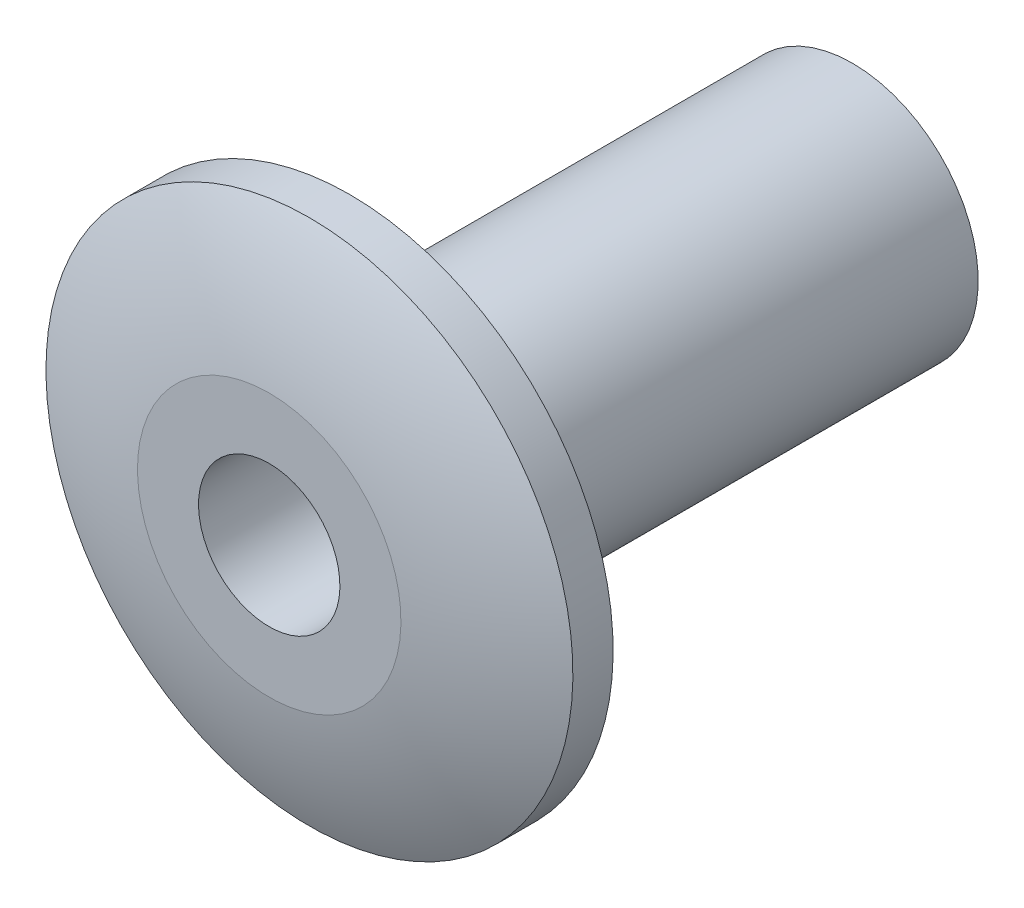
SolidWorks part; units mm, degrees
material "3003-H14"
ref_plane "Front" through (0, 0, 0) normal (0, 0, 1) x (1, 0, 0)
ref_plane "Top" through (0, 0, 0) normal (0, 1, 0) x (1, 0, 0)
ref_plane "Right" through (0, 0, 0) normal (1, 0, 0) x (0, 0, -1)
sketch "Sketch1" plane through (0, 0, 0) normal (1, 0, 0) x (0, 0, -1)
  line L0 (-10.541, 0) -> (-1.016, 0) construction
  line L1 (-1.016, 0) -> (0, 0) construction
  line L2 (0, 0) -> (6.35, 0) construction
  line L3 (6.35, 0) -> (7.874, 0) construction
  line L8 (0, 3.3274) -> (0, -3.3274) construction
  line L9 (6.35, 1.5875) -> (6.35, -1.5875) construction
  dimension "Length" = 6.35
  dimension "Head Height" = 1.016
  dimension "D5" = 1.524
  dimension "D9" = 9.525
  dimension "Diameter" = 3.175
  dimension "Head Diameter" = 6.6548
sketch "Sketch2" plane through (0, 0, 0) normal (1, 0, 0) x (0, 0, -1)
  line L0 (-10.541, 0.7937) -> (-10.541, 0) construction
  line L1 (-10.541, 0.7937) -> (0, 0.7937) construction
  line L2 (0, 3.3274) -> (0, -3.3274) construction
  line L3 (0, 0) -> (0, 3.3274) construction
  line L4 (-1.016, 0) -> (-1.016, -1.8472) construction
  line L5 (6.35, 1.5875) -> (0, 1.5875)
  line L6 (6.35, 1.5875) -> (6.35, 0) construction
  line L7 (7.874, 0) -> (7.874, 1.5875) construction
  line L8 (6.35, 1.5875) -> (6.35, 0)
  line L9 (7.874, 1.5875) -> (6.35, 1.5875) construction
  line L10 (-1.016, 0.893) -> (-1.016, 1.6637)
  line L11 (6.35, 0) -> (7.874, 0) construction
  line L12 (6.35, 0) -> (0.635, 0)
  line L13 (-1.016, 0.7937) -> (-1.016, 0) construction
  line L14 (6.35, 1.5875) -> (6.35, 0) construction
  line L15 (6.35, 1.5875) -> (6.35, 0) construction
  line L16 (6.35, 0) -> (6.35, 1.5875) construction
  line L17 (6.35, 1.5875) -> (6.35, 0) construction
  line L18 (6.35, 0) -> (6.35, 1.5875) construction
  line L19 (0, 1.5875) -> (0, 3.3274)
  line L20 (-1.016, 0.893) -> (0, 0.893)
  line L21 (-10.541, 0.893) -> (0, 0.893) construction
  line L22 (0, 3.3274) -> (-0.508, 3.3274)
  line L23 (0, 0.893) -> (0.635, 0.893)
  line L24 (0.635, 0.893) -> (0.635, 0)
  arc A0 (7.874, 0) -> (6.35, 1.27) centre (6.5828, 0) ccw construction
  arc A2 (-0.508, 3.3274) -> (-1.016, 1.6637) centre (4.8114, 0.7937) ccw
  dimension "D3" = 0.508
  dimension "D1" = 0.7937
  dimension "D2" = 0.635
  dimension "D5" = 1.27
  dimension "D6" = 1.6637
  dimension "D4" = 0.0992
revolve "Revolve1" add sketch "Sketch2" angle 360 about L12
sketch "Sketch7" plane through (0, 0, 0) normal (1, 0, 0) x (0, 0, -1)
  line L0 (-9.788, 0.7937) -> (0.635, 0.7937)
  line L1 (0.635, 0.893) -> (0.635, 0) construction
  line L2 (0.635, 0.7937) -> (0.635, 0)
  line L3 (0.635, 0) -> (-10.541, 0)
  line L5 (-10.417, 0.266) -> (-9.788, 0.7937)
  arc A0 (-10.541, 0) -> (-10.417, 0.266) centre (-10.1937, 0) cw
  dimension "D1" = 0.3473
  dimension "D2" = 40
revolve "Revolve2" [suppressed] add sketch "Sketch7" angle 360 about L0
sketch "Sketch8" plane through (0, 0, 0) normal (1, 0, 0) x (0, 0, -1)
  line L1 (6.35, 1.27) -> (6.35, 0)
  line L2 (6.35, 0) -> (7.874, 0) construction
  line L3 (7.874, 0) -> (6.5828, 0) construction
  line L4 (7.5512, 0) -> (6.35, 0)
  line L5 (6.35, 1.27) -> (6.6992, 1.27) construction
  arc A0 (7.874, 0) -> (6.35, 1.27) centre (6.5828, 0) ccw construction
  arc A1 (6.6993, 1.2859) -> (6.35, 1.27) centre (6.5828, 0) ccw
  arc A2 (6.6993, 1.2859) -> (7.5512, 0) centre (6.1548, 0) cw
  circle A3 centre (6.5828, 0) radius 1.2912 construction
  point P7 (7.5512, 0)
  point P8 (7.2284, 0)
  point P9 (6.9056, 0)
  point P12 (6.4664, 1.27)
  point P13 (6.5828, 1.27)
revolve "Revolve3" [suppressed] add sketch "Sketch8" angle 360 about L3
sketch "Sketch3" [suppressed] plane through (0, 0, 0) normal (0, 1, 0) x (1, 0, 0)
  line L0 (-0.997, -8.4087) -> (-0.2209, -10.541)
  line L1 (-0.2209, -10.541) -> (0.2209, -10.541)
  line L3 (0, -10.541) -> (0, -11.049) construction
  line L4 (0.266, -10.417) -> (-0.266, -10.417) construction
  line L5 (-0.997, -8.4087) -> (-0.997, -11.049)
  line L6 (-0.997, -11.049) -> (0.9969, -11.049)
  line L7 (0.9969, -11.049) -> (0.9969, -8.4087)
  line L8 (-0.7937, 0.635) -> (-0.7937, -9.788) construction
  line L9 (0, -10.541) -> (0, -1.016) construction
  line L10 (0.2209, -10.541) -> (0.9969, -8.4087)
  line L11 (-0.7937, -9.788) -> (-0.266, -10.417) construction
  arc A0 (-0.266, -10.417) -> (0.266, -10.417) centre (0, -10.1937) ccw construction
  point P11 (-0.266, -10.417)
  point P25 (0, -10.541)
  dimension "D1" = 40
  dimension "D2" = 0.2032
  dimension "D3" = 0.508
extrude "Cut-Extrude1" [suppressed] cut sketch "Sketch3" against normal through all both and the other way through all
pattern_circular "CirPattern1" [suppressed] count 2 every 90 about axis through (0, 0, 10.541) along (0, 0, -1) of bodies 111
sketch "Sketch9" [suppressed] plane through (0, 0, 0) normal (0, 1, 0) x (1, 0, 0)
  line L0 (0, -10.541) -> (0, 19.9517) construction
  line L1 (0, 6.35) -> (0, 7.874) construction
  line L2 (3.3274, 0) -> (-3.3274, 0) construction
  line L3 (2.0356, 0) -> (2.1341, 0)
  line L4 (2.0356, 0) -> (2.0356, 0.0254)
  line L5 (2.0356, 0.0254) -> (2.1341, 0.0254)
  line L6 (2.1341, 0) -> (2.1341, 0.0254)
  line L8 (2.3081, 0) -> (2.4066, 0)
  line L9 (2.3081, 0) -> (2.3081, 0.0254)
  line L10 (2.3081, 0.0254) -> (2.4066, 0.0254)
  line L11 (2.4066, 0) -> (2.4066, 0.0254)
  line L12 (2.551, 0) -> (2.6495, 0)
  line L13 (2.551, 0) -> (2.551, 0.0254)
  line L14 (2.551, 0.0254) -> (2.6495, 0.0254)
  line L15 (2.6495, 0) -> (2.6495, 0.0254)
  line L16 (2.9023, 0) -> (3.0008, 0)
  line L17 (2.9023, 0) -> (2.9023, 0.0254)
  line L18 (2.9023, 0.0254) -> (3.0008, 0.0254)
  line L19 (3.0008, 0) -> (3.0008, 0.0254)
  line L20 (1.9076, 0) -> (1.8091, 0)
  line L21 (1.9076, 0) -> (1.9076, 0.0254)
  line L22 (1.9076, 0.0254) -> (1.8091, 0.0254)
  line L23 (1.8091, 0) -> (1.8091, 0.0254)
  point P24 (2.9515, 0.0254)
  point P25 (2.6003, 0.0254)
  point P26 (2.3573, 0.0254)
  point P27 (2.0848, 0.0254)
  point P32 (1.8583, 0.0254)
  dimension "D1" = 0.0985
  dimension "D2" = 0.0254
  dimension "D3" = 5.903
  dimension "D4" = 5.2005
  dimension "D5" = 4.7146
  dimension "D6" = 4.1697
  dimension "D7" = 3.7167
revolve "Revolve4" [suppressed] add sketch "Sketch9" angle 360 about L0
equation "\"D5@Sketch1\" = \"Head Height@Sketch1\" * 1.5"
equation "\"D9@Sketch1\" = \"Length@Sketch1\" * 1.5"
equation "\"D1@Sketch2\"=\"Diameter@Sketch1\"/4"
equation "\"D4@Sketch2\"=\"D1@Sketch2\"/8"
equation "\"D2@Sketch2\"=\"Length@Sketch1\"/10"
equation "\"D5@Sketch2\"=\"Diameter@Sketch1\"*.8/2"
equation "\"D1@Sketch7\"=(\"D1@Sketch2\"-\"D4@Sketch2\")*2*.25"
equation "\"D6@Sketch2\"=\"Head Diameter@Sketch1\"/2*.5"
equation "\"D7@Sketch9\"=.15566*(\"Head Diameter@Sketch1\"-\"Diameter@Sketch1\")+\"Diameter@Sketch1\""
equation "\"D3@Sketch9\"=.7839623*(\"Head Diameter@Sketch1\"-\"Diameter@Sketch1\")+\"Diameter@Sketch1\""
equation "\"D1@Sketch9\"=.028302*(\"Head Diameter@Sketch1\"-\"Diameter@Sketch1\")"
equation "\"D6@Sketch9\"=.285849*(\"Head Diameter@Sketch1\"-\"Diameter@Sketch1\")+\"Diameter@Sketch1\""
equation "\"D5@Sketch9\"=.4424528*(\"Head Diameter@Sketch1\"-\"Diameter@Sketch1\")+\"Diameter@Sketch1\""
equation "\"D4@Sketch9\"=.582075*(\"Head Diameter@Sketch1\"-\"Diameter@Sketch1\")+\"Diameter@Sketch1\""
